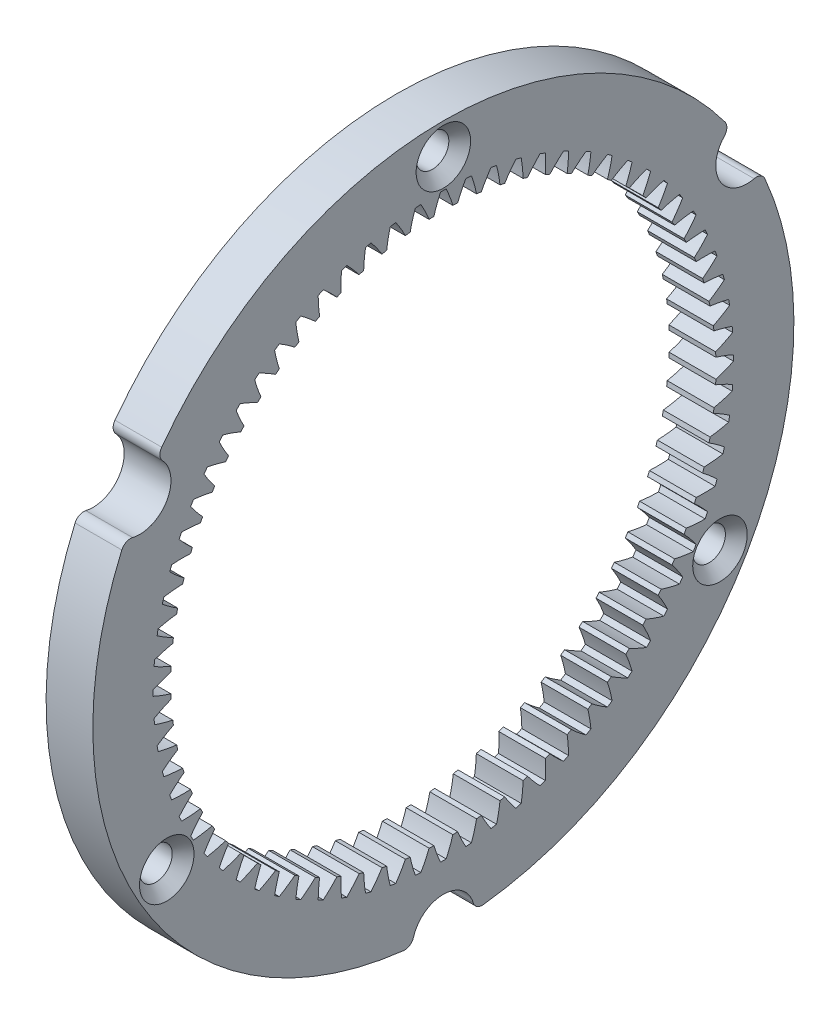
SolidWorks part; units mm, degrees
ref_plane "Plane1" through (0, 0, 0) normal (0, 0, 1) x (1, 0, 0)
ref_plane "Plane2" through (0, 0, 0) normal (0, 1, 0) x (1, 0, 0)
ref_plane "Plane3" through (0, 0, 0) normal (1, 0, 0) x (0, 0, -1)
sketch "HoldingSke" plane through (0, 0, 0) normal (0, 1, 0) x (1, 0, 0)
  line L0 (0, 0) -> (0.618, -1.9021)
  line L1 (-15, 0) -> (100, 0) construction
  line L2 (0, 0) -> (-2.1039, 2.3779)
  line L3 (0, 0) -> (-11.863, 4.5341)
  line L4 (0, 0) -> (2.6687, 8.2133)
  line L5 (0, 0) -> (-23.7986, -8.8762)
  line L6 (0, 0) -> (-10.5278, -7.1032)
  line L7 (-2.1039, 2.3779) -> (3.3635, 27.1825)
  line L8 (-76.2, 2.8779) -> (-54.61, 2.8779)
  line L9 (-71.009, 38.7566) -> (-53.1078, 45.2721)
  line L10 (-76.2, 71.12) -> (104.1128, 71.12)
  line L11 (0, 0) -> (-4, 0)
  line L12 (-76.2, 101.6) -> (-76.181, 101.6)
  line L13 (24.9733, 27.94) -> (52.9518, 28.4284)
  line L14 (24.9733, 27.94) -> (24.9743, 27.94)
  line L15 (24.9733, 27.94) -> (100.4006, 29.5858)
  circle A0 centre (0, 0) radius 22.5
  circle A1 centre (0, 0) radius 12.7
  circle A2 centre (0, 0) radius 12.7
  dimension "Num_teeth" = 72
  dimension "Pitch_radius" = 180.3128
  dimension "Width" = 4
  dimension "Diameter" = 45
sketch "BasProSke" plane through (0, 0, 0) normal (0, 1, 0) x (1, 0, 0)
  line L0 (-10, 0) -> (60, 0) construction
  line L1 (0, 17.5) -> (0, 22.5)
  line L2 (0, 17.5) -> (3, 17.5)
  line L3 (3, 17.5) -> (3, 22.5)
  line L4 (3, 22.5) -> (0, 22.5)
  dimension "Thickness" = 3
  dimension "Diameter" = 45
revolve "Base-Revolve" add sketch "BasProSke" angle 360 about L0
sketch "TooCutSke" plane through (0, 0, 0) normal (1, 0, 0) x (0, 0, -1)
  line L3 (0.4402, 17.9946) -> (0.4402, 53.6633) construction
  line L4 (0, 0) -> (0, 59.563) construction
  line L5 (0, 0) -> (-2.9804, 68.2625) construction
  line L6 (-8.0066, 14.8879) -> (37.1428, 16.8592) construction
  circle A0 centre (0, 0) radius 18 construction
  circle A1 centre (0, 0) radius 18.626 construction
  circle A2 centre (0, 0) radius 15.223 construction
  circle A3 centre (0, 0) radius 17.4746 construction
  arc A4 (0.6169, 17.4637) -> (0.1808, 18.6251) centre (-8.0066, 14.8879) ccw
  arc A5 (0.6169, 17.4637) -> (-0.6169, 17.4637) centre (0, 0) ccw
  arc A6 (0.1808, 18.6251) -> (-0.1808, 18.6251) centre (0, 0) ccw
  arc A7 (-0.1808, 18.6251) -> (-0.6169, 17.4637) centre (8.0066, 14.8879) ccw
extrude "ToothCut" cut sketch "TooCutSke" along normal through all
fillet "Breaks" [suppressed] radius 0.05
fillet "RootFillets" [suppressed] radius 0.126
pattern_circular "TeethCuts" count 72 every 5 about axis through (-10, 0, 0) along (1, 0, 0) of "RootFillets", "Breaks", "ToothCut"
sketch "Sketch1" plane through (3, 0, 0) normal (1, 0, 0) x (0, 0, -1)
  line L0 (0, 0) -> (19.2637, 7.0114) construction
  line L1 (19.2637, 7.0114) -> (15.7039, 13.1771) construction
  line L2 (15.7039, 13.1771) -> (0, 0) construction
  line L3 (0, 0) -> (0, 22.5) construction
  circle A0 centre (15.7039, 13.1771) radius 1.05
  circle A1 centre (19.2637, 7.0114) radius 1.05
  circle A2 centre (0, 0) radius 22.5 construction
  dimension "D1" = 20.5
  dimension "D4" = 2.1
  dimension "D5" = 2.1
  dimension "D2" = 20.5
  dimension "D3" = 20
  dimension "D6" = 50
extrude "Cut-Extrude1" [suppressed] cut sketch "Sketch1" against normal through all
pattern_circular "CirPattern1" [suppressed] count 3 over 360 of bodies 103
sketch "Sketch2" plane through (3, 0, 0) normal (1, 0, 0) x (0, 0, -1)
  circle A0 centre (0, 20.5) radius 1.05
  circle A1 centre (17.7535, -10.25) radius 1.05
  circle A2 centre (-17.7535, -10.25) radius 1.05
  point P2 (0, 0)
  point P10 (0, 0)
  dimension "D2" = 2.1
  dimension "D1" = 20.5
  dimension "D3" = 3
extrude "Cut-Extrude2" cut sketch "Sketch2" against normal blind 10
sketch "Sketch3" plane through (3, 0, 0) normal (1, 0, 0) x (0, 0, -1)
  line L0 (0, 20.5) -> (17.7535, -10.25) construction
  line L1 (0, 0) -> (19.4856, 11.25) construction
  circle A0 centre (19.4856, 11.25) radius 2
  circle A1 centre (0, 0) radius 22.5 construction
  circle A2 centre (0, -22.5) radius 2
  circle A3 centre (-19.4856, 11.25) radius 2
  point P16 (0, 0)
  dimension "D1" = 4
  dimension "D2" = 3
extrude "Cut-Extrude3" cut sketch "Sketch3" against normal blind 10
fillet "Fillet1" radius 0.6 6 edges at (1.5, 9.4752, 20.4076) (1.5, 12.9359, 18.4096) (1.5, 9.4752, -20.4076) (1.5, -22.4111, -1.998) (1.5, -22.4111, 1.998) (1.5, 12.9359, -18.4096)
chamfer "Chamfer1" distance 0.7 angle 45 3 edges at (3, -10.25, -18.8035) (3, -10.25, 16.7035) (3, 20.5, -1.05)
equation "' \"Module@HoldingSke\" = 6.35"
equation "' \"Num_teeth@HoldingSke\" = 24"
equation "' \"Ap@HoldingSke\" =  14.5"
equation "' \"Ap@HoldingSke\" = 14.5"
equation "' \"Width@HoldingSke\" = 12"
equation "' \"Diameter@HoldingSke\" = 8 * 25.4"
equation "' \"Show_teeth@HoldingSke\" = 100"
equation "' \"Backlash@HoldingSke\" = 0.009 * 25.4"
equation "' \"Addendum_fac@HoldingSke\" = 1.0"
equation "' \"Dedendum_fac@HoldingSke\" = 1.25"
equation "' \"Dedendum_add@HoldingSke\" = 0.00005 * 25.4"
equation "' \"Clearance_fac@HoldingSke\" = 0.25"
equation "\"Pitch@HoldingSke\" = 1 / \"Module@HoldingSke\" "
equation "\"Overcut_dia@TooCutSke\" = (\"Num_teeth@HoldingSke\" - 2 * \"Addendum_fac@HoldingSke\") / \"Pitch@HoldingSke\" - 0.002 * 25.4"
equation "\"Pitch_dia@TooCutSke\" = \"Num_teeth@HoldingSke\" / \"Pitch@HoldingSke\""
equation "\"Base_dia@TooCutSke\" = \"Num_teeth@HoldingSke\" / \"Pitch@HoldingSke\" * cos((\"Ap@HoldingSke\"  * 3.14159265 / 180)) * 0.90"
equation "\"Root_dia@TooCutSke\" = \"Num_teeth@HoldingSke\"  / \"Pitch@HoldingSke\" + 2 *  \"Dedendum_fac@HoldingSke\"/ \"Pitch@HoldingSke\" + \"Dedendum_add@HoldingSke\" * 2"
equation "\"Half_ang@TooCutSke\" = 180 / \"Num_teeth@HoldingSke\""
equation "\"Half_CT@TooCutSke\" = \"Num_teeth@HoldingSke\" / \"Pitch@HoldingSke\" * sin((3.14159265 / 2 / \"Num_teeth@HoldingSke\")) / 2 + 10 * \"Backlash@HoldingSke\" / 4"
equation "\"Flank_rad@TooCutSke\" = \"Num_teeth@HoldingSke\" / \"Pitch@HoldingSke\" / 4"
equation "\"Radius@RootFillets\"= \"Clearance_fac@HoldingSke\" / \"Pitch@HoldingSke\" + \"Dedendum_add@HoldingSke\""
equation "\"Break_rad@Breaks\" = 0.02 / \"Pitch@HoldingSke\" * 5"
equation "\"Num_teeth@TeethCuts\" = int( \"Show_teeth@HoldingSke\" ) + 1"
equation "\"Num_teeth@TeethCuts\" = ((sgn( \"Num_teeth@TeethCuts\" - \"Num_teeth@HoldingSke\" )-1)*( \"Num_teeth@TeethCuts\" - \"Num_teeth@HoldingSke\" ))/-2+ \"Num_teeth@HoldingSke\""
equation "\"Num_teeth@TeethCuts\" = ((sgn( \"Num_teeth@TeethCuts\" - 2.0)+1)*( \"Num_teeth@TeethCuts\" - 2.0))/2 +2.0"
equation "\"Angle@TeethCuts\" = 360.0 / \"Num_teeth@HoldingSke\""
equation "\"Diameter@BasProSke\" = \"Num_teeth@HoldingSke\"  / \"Pitch@HoldingSke\" + 2 *  \"Dedendum_fac@HoldingSke\"/ \"Pitch@HoldingSke\" + \"Dedendum_add@HoldingSke\" * 2 + 0.002 * 25.4"
equation "\"Diameter@BasProSke\" = ((sgn( \"Diameter@BasProSke\"  - \"Diameter@HoldingSke\" )+1)*( \"Diameter@BasProSke\"  - \"Diameter@HoldingSke\" ))/2 + \"Diameter@HoldingSke\""
equation "\"Inside_diameter@BasProSke\" =  (\"Num_teeth@HoldingSke\" - 2 * \"Addendum_fac@HoldingSke\") / \"Pitch@HoldingSke\" "
equation "\"Thickness@BasProSke\"=3"
